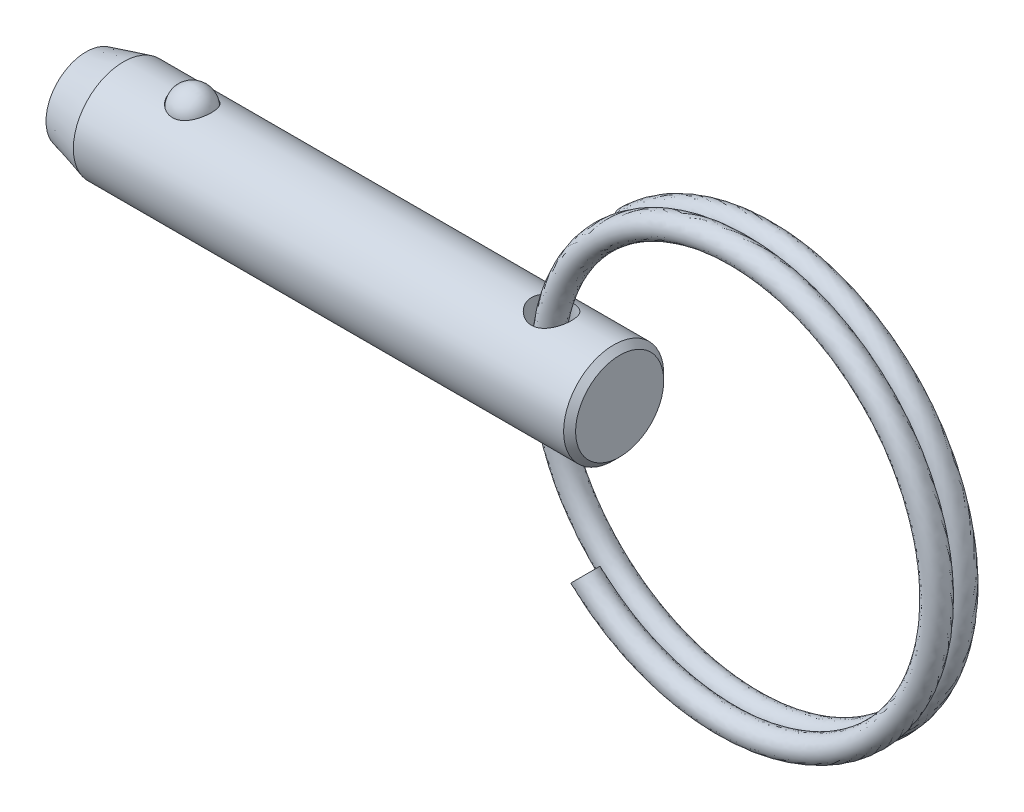
SolidWorks part; units mm, degrees
material "AISI 304"
ref_plane "Front" through (0, 0, 0) normal (0, 0, 1) x (1, 0, 0)
ref_plane "Top" through (0, 0, 0) normal (0, 1, 0) x (1, 0, 0)
ref_plane "Right" through (0, 0, 0) normal (1, 0, 0) x (0, 0, -1)
sketch "Sketch1" plane through (0, 0, 0) normal (0, 0, 1) x (1, 0, 0)
  line L0 (5.588, 2.794) -> (5.207, 3.175)
  line L1 (5.207, 3.175) -> (5.588, 3.175) construction
  line L4 (5.588, 2.794) -> (5.588, 0)
  line L5 (5.588, 3.175) -> (5.588, 2.794) construction
  line L16 (5.207, 3.175) -> (-25.8749, 3.175)
  line L17 (-28.2448, 3.175) -> (-28.2448, 2.54) construction
  line L19 (-25.8749, 3.175) -> (-28.2448, 3.175) construction
  line L22 (-28.2448, -3.175) -> (-25.8749, -3.175) construction
  line L23 (-21.5103, 2.8575) -> (-21.5103, -2.8575) construction
  line L24 (-28.2448, 0) -> (5.588, 0)
  line L27 (5.588, 0) -> (8.382, 0) construction
  line L29 (-28.2448, 0) -> (-28.2448, -2.54) construction
  line L36 (0, 0) -> (0, 3.175) construction
  line L37 (-28.2448, 2.54) -> (-28.2448, 0)
  line L38 (-25.8749, -3.175) -> (5.588, -3.175) construction
  line L39 (-28.2448, -2.54) -> (-28.2448, -3.175) construction
  line L40 (-25.8749, 3.175) -> (-28.2448, 2.54)
  line L42 (-25.8749, -3.175) -> (-28.2448, -2.54) construction
  line L43 (-25.8749, 3.175) -> (-25.8749, -3.175) construction
  circle A2 centre (-21.5103, 2.8575) radius 1.2319 construction
  point P35 (-20.32, 3.175)
  dimension "D2" = 5.715
  dimension "D11" = 0.9144
  dimension "A" = 6.35
  dimension "D" = 5.588
  dimension "E" = 7.2644
  dimension "D3" = 0.381
  dimension "Useable Length" = 20.32
  dimension "D12" = 5.08
  dimension "C" = 7.9248
  dimension "A1" = 15
revolve "Revolve1" add sketch "Sketch1" angle 360 about L27
sketch "Sketch2" plane through (0, 0, 0) normal (0, 0, 1) x (1, 0, 0)
  line L0 (-20.253, 2.8575) -> (-22.7676, 2.8575)
  line L1 (-21.5103, 4.0894) -> (-21.5103, 4.1148) construction
  line L2 (-20.253, 2.8575) -> (-17.7384, 2.8575) construction
  circle A0 centre (-21.5103, 2.8575) radius 1.2319 construction
  circle A1 centre (-21.5103, 2.8575) radius 1.2319 construction
  arc A2 (-22.7676, 2.8575) -> (-20.253, 2.8575) centre (-21.5103, 2.8575) cw
  dimension "D1" = 0.0254
revolve "Cut-Revolve1" cut sketch "Sketch2" angle 360 about L2
sketch "Sketch3" plane through (0, 0, 0) normal (0, 0, 1) x (1, 0, 0)
  line L0 (-20.2784, 2.8575) -> (-22.7422, 2.8575)
  line L1 (-20.2784, 2.8575) -> (-17.8146, 2.8575) construction
  circle A0 centre (-21.5103, 2.8575) radius 1.2319 construction
  arc A1 (-20.2784, 2.8575) -> (-22.7422, 2.8575) centre (-21.5103, 2.8575) ccw
revolve "Revolve2" add sketch "Sketch3" angle 360 about L1
sketch "Sketch4" plane through (0, 0, 0) normal (0, 0, 1) x (1, 0, 0)
  line L1 (1.27, -3.175) -> (2.54, -3.175)
  line L2 (1.27, -3.175) -> (1.27, 3.175)
  line L3 (1.27, 3.175) -> (2.54, 3.175)
  line L4 (2.54, -3.175) -> (2.54, 3.175)
  line L5 (1.27, -3.175) -> (1.27, -4.445) construction
  line L6 (2.54, 3.175) -> (5.588, 3.175) construction
  line L8 (0, -3.175) -> (0, 3.175) construction
  line L9 (0, 0) -> (1.27, 0) construction
  line L11 (1.27, 0) -> (2.54, 0) construction
  line L12 (5.207, 3.175) -> (-25.8749, 3.175) construction
  line L14 (-25.8749, -3.175) -> (5.588, -3.175) construction
  dimension "D1" = 2.54
revolve "Cut-Revolve2" cut sketch "Sketch4" angle 360 about L2
sketch "Sketch5" plane through (0, 0, 0) normal (0, 0, 1) x (1, 0, 0)
  line L0 (0, 0) -> (0.293, 0) construction
  line L1 (0.293, 0) -> (0.293, 3.175) construction
  line L2 (5.207, 3.175) -> (-25.8749, 3.175) construction
  line L3 (13.755, 0) -> (27.217, 0) construction
  line L4 (2.54, 3.175) -> (2.247, 3.175) construction
  line L5 (1.27, 3.175) -> (2.54, 3.175) construction
  line L6 (0.6728, 3.175) -> (0.6728, -3.175) construction
  line L7 (0.293, 3.175) -> (0, 3.175) construction
  line L8 (1.27, -3.175) -> (2.54, -3.175) construction
  line L9 (0.6728, -3.175) -> (2.54, -3.175) construction
  line L10 (0.293, 0) -> (13.755, 0) construction
  line L11 (13.755, 0) -> (8.7098, -10.8195) construction
  line L12 (2.247, 3.175) -> (0.6728, 3.175) construction
  line L13 (13.755, 11.938) -> (13.755, 13.462) construction
  line L14 (8.7098, -10.8195) -> (8.3878, -11.5101) construction
  circle A0 centre (13.755, 0) radius 13.462
  circle A1 centre (13.755, 0) radius 11.938 construction
  circle A2 centre (13.755, 0) radius 12.7 construction
  point P26 (13.755, 12.7)
  dimension "D1" = 65
  dimension "R Ring Dia" = 25.4
  dimension "Ring OD" = 1.524
curve "Helix/Spiral1" pitch 1.5494 height 1.3557 radius 13.462 left hand yes centre (13.755, 0, 0) axis (0, 0, -1) start towards (1, 0, 0)
sketch "Sketch6" plane through (114.0038, 0, 0) normal (0, 1, 0) x (0, 0, -1)
  line L0 (0, 112.1868) -> (0, 112.9488) construction
  line L1 (0, 112.9488) -> (0, 113.7108) construction
  circle A0 centre (0, 112.9488) radius 0.762
  dimension "D1" = 1.524
sketch "Sketch7" plane through (0, 0, 0) normal (0, 0, 1) x (1, 0, 0)
  circle A0 centre (13.755, 0) radius 13.462 construction
  circle A1 centre (13.755, 0) radius 13.462
curve "Helix/Spiral2" pitch 1.5494 height 1.3557 radius 13.462 left hand yes centre (13.755, 0, 0) axis (0, 0, 1) start towards (1, 0, 0)
sweep "Sweep1" add profiles "Sketch6" path "Helix/Spiral1"
sweep "Sweep2" add profiles "Sketch6<2>" path "Helix/Spiral2"
sketch "Sketch6<2>" plane through (114.0038, 0, 0) normal (0, 1, 0) x (0, 0, -1) same geometry as "Sketch6"
ref_plane "Plane1" through (0, -10.8195, 0) normal (0, 1, 0) x (-1, 0, 0)
sketch "Sketch8" plane through (0, -10.8195, 0) normal (0, 1, 0) x (-1, 0, 0)
  line L0 (143.6902, 0) -> (-8.7098, 0) construction
  line L1 (10.3402, -0.7779) -> (4.5066, -0.7779)
  line L2 (3.5004, -0.9415) -> (-7.2005, -4.517)
  line L3 (-7.2005, 4.517) -> (3.5004, 0.9415)
  line L4 (4.5066, 0.7779) -> (130.4738, 0.7779)
  line L5 (131.48, 0.9415) -> (142.1809, 4.517)
  line L6 (124.6402, -0.7779) -> (130.4738, -0.7779)
  line L7 (131.48, -0.9415) -> (142.1809, -4.517)
  line L8 (10.3402, -0.7779) -> (10.3402, 0.7779) construction
  arc A0 (-7.2005, 4.517) -> (-7.2005, -4.517) centre (-8.7098, 0) ccw
  arc A1 (142.1809, -4.517) -> (142.1809, 4.517) centre (143.6902, 0) ccw
  arc A2 (4.5066, -0.7779) -> (3.5004, -0.9415) centre (4.5066, -3.9529) ccw
  arc A3 (3.5004, 0.9415) -> (4.5066, 0.7779) centre (4.5066, 3.9529) ccw
  arc A4 (130.4738, -0.7779) -> (131.48, -0.9415) centre (130.4738, -3.9529) cw
  arc A5 (130.4738, 0.7779) -> (131.48, 0.9415) centre (130.4738, 3.9529) ccw
  point P6 (10.3402, 0)
  point P16 (3.9902, -0.7779)
  point P20 (3.9902, 0.7779)
  point P23 (130.9902, -0.7779)
  point P26 (130.9902, 0.7779)
  dimension "D2" = 4.7625
  dimension "D3" = 1.5557
  dimension "D6" = 3.175
  dimension "Lanyard Length" = 152.4
  dimension "D4" = 6.35
  dimension "D5" = 12.7
ref_plane "Plane2" through (-10.3402, 0, 0) normal (1, 0, 0) x (0, 0, -1)
sketch "Sketch9" plane through (-10.3402, 0, 0) normal (1, 0, 0) x (0, 0, -1)
  circle A0 centre (0.7779, -10.8195) radius 0.7779
sweep "Sweep3" [suppressed] add profiles "Sketch9" path "Sketch8"
sketch "Sketch10" [suppressed] plane through (-10.3402, 0, 0) normal (1, 0, 0) x (0, 0, -1)
  arc A0 (-0.3849, -10.1482) -> (-0.3849, -11.4908) centre (-0.7779, -10.8195) ccw
  circle A1 centre (0.7779, -10.8195) radius 0.7779
  arc A2 (0.3849, -11.4908) -> (0.3849, -10.1482) centre (0.7779, -10.8195) ccw
  arc A3 (-0.3849, -11.4908) -> (0.3849, -11.4908) centre (0, -12.1485) cw
  arc A4 (-0.3869, -9.3301) -> (-0.3869, -12.3089) centre (-0.7779, -10.8195) ccw
  arc A5 (0.3869, -12.3089) -> (0.3869, -9.3301) centre (0.7779, -10.8195) ccw
  circle A6 centre (-0.7779, -10.8195) radius 1.5399 construction
  circle A7 centre (-0.7779, -10.8195) radius 0.7779 construction
  arc A8 (-0.3849, -10.1482) -> (0.3849, -10.1482) centre (0, -9.4905) ccw
  arc A9 (-0.3869, -9.3301) -> (0.3869, -9.3301) centre (0, -7.856) ccw
  arc A10 (0.3869, -12.3089) -> (-0.3869, -12.3089) centre (0, -13.783) ccw
  point P4 (-0.034, -10.2746)
  point P8 (2.3178, -10.502)
  point P9 (0.762, -10.502)
  dimension "D3" = 1.524
  dimension "D4" = 0.762
  dimension "D2" = 0.762
  dimension "D1" = 0
extrude "Extrude1" [suppressed] add sketch "Sketch10" along normal blind 5.715 separate body
sketch "Sketch11" [suppressed] plane through (-124.6402, 0, 0) normal (1, 0, 0) x (0, 0, -1)
  arc A4 (-0.3849, -10.1482) -> (-0.3849, -11.4908) centre (-0.7779, -10.8195) ccw
  arc A5 (0.3849, -11.4908) -> (-0.3849, -11.4908) centre (0, -12.1485) ccw
  arc A6 (0.3849, -11.4908) -> (0.3849, -10.1482) centre (0.7779, -10.8195) ccw
  arc A7 (-0.3849, -10.1482) -> (0.3849, -10.1482) centre (0, -9.4905) ccw
  arc A8 (-0.3849, -10.1482) -> (-0.3849, -11.4908) centre (-0.7779, -10.8195) ccw
  arc A9 (0.3849, -11.4908) -> (-0.3849, -11.4908) centre (0, -12.1485) ccw
  arc A10 (0.3849, -11.4908) -> (0.3849, -10.1482) centre (0.7779, -10.8195) ccw
  arc A11 (-0.3849, -10.1482) -> (0.3849, -10.1482) centre (0, -9.4905) ccw
  arc A12 (-0.3869, -9.3301) -> (-0.3869, -12.3089) centre (-0.7779, -10.8195) ccw
  arc A13 (0.3869, -12.3089) -> (-0.3869, -12.3089) centre (0, -13.783) ccw
  arc A14 (0.3869, -12.3089) -> (0.3869, -9.3301) centre (0.7779, -10.8195) ccw
  arc A15 (-0.3869, -9.3301) -> (0.3869, -9.3301) centre (0, -7.856) ccw
  arc A16 (-0.3869, -9.3301) -> (-0.3869, -12.3089) centre (-0.7779, -10.8195) ccw
  arc A17 (0.3869, -12.3089) -> (-0.3869, -12.3089) centre (0, -13.783) ccw
  arc A18 (0.3869, -12.3089) -> (0.3869, -9.3301) centre (0.7779, -10.8195) ccw
  arc A19 (-0.3869, -9.3301) -> (0.3869, -9.3301) centre (0, -7.856) ccw
  dimension "D1" = 0
  dimension "D2" = 0
extrude "Extrude2" [suppressed] add sketch "Sketch11" against normal blind 5.715 separate body
sketch "Sketch12" plane through (0, -10.8195, 0) normal (0, 1, 0) x (-1, 0, 0)
  line L0 (174.4712, -5.2864) -> (168.9086, -5.2864) construction
  line L1 (174.4712, -5.9214) -> (158.1026, -5.9214)
  line L2 (174.4712, -5.9214) -> (174.4712, -4.6514)
  line L3 (174.4712, -4.6514) -> (158.3265, -4.6514)
  line L4 (158.1026, -5.9214) -> (158.3265, -4.6514) construction
  line L5 (158.1026, -5.9214) -> (142.7212, -0.3231)
  line L6 (168.9086, -5.2864) -> (158.2146, -5.2864) construction
  line L7 (158.3265, -4.6514) -> (143.1555, 0.8704)
  line L8 (142.7212, -0.3231) -> (143.1555, 0.8704)
  line L9 (158.2146, -5.2864) -> (148.1655, -1.6289) construction
  line L10 (148.1655, -1.6289) -> (142.9383, 0.2737) construction
  arc A0 (142.1809, -4.517) -> (142.1809, 4.517) centre (143.6902, 0) ccw construction
  dimension "D1" = 20
  dimension "D2" = 31.75
  dimension "D3" = 1.27
  dimension "D4" = 5.5626
extrude "Extrude3" [suppressed] add sketch "Sketch12" along normal mid plane 12.7 separate body
sketch "Sketch13" [suppressed] plane through (0, 0, -4.6514) normal (0, 0, 1) x (1, 0, 0)
  line L0 (-174.4712, -10.8195) -> (-158.3265, -10.8195) construction
  line L1 (-172.4782, -4.4695) -> (-174.4712, -4.4695)
  line L2 (-174.4712, -4.4695) -> (-158.3265, -4.4695) construction
  line L3 (-174.4712, -4.4695) -> (-176.4642, -4.4695)
  line L4 (-176.4642, -4.4695) -> (-176.4642, -17.1695)
  line L5 (-176.4642, -17.1695) -> (-174.4712, -17.1695)
  line L6 (-174.4712, -17.1695) -> (-172.4782, -17.1695)
  line L7 (-174.4712, -17.1695) -> (-158.3265, -17.1695) construction
  arc A0 (-172.4782, -4.4695) -> (-172.4782, -17.1695) centre (-163.3587, -10.8195) ccw
  circle A1 centre (-168.9086, -10.8195) radius 2.5781
  dimension "D1" = 5.1562
  dimension "D2" = 11.1125
extrude "Extrude4" [suppressed] cut sketch "Sketch13" against normal up to surface (1.27 mm away)
sketch "Sketch14" [suppressed] plane through (-17.0257, 0, 46.7778) normal (-0.342, 0, 0.9397) x (0.9397, 0, 0.342)
  line L3 (-136.2175, -4.4695) -> (-134.2245, -4.4695)
  line L4 (-134.2245, -4.4695) -> (-132.2315, -4.4695)
  line L5 (-132.2315, -4.4695) -> (-132.2315, -17.1695)
  line L6 (-132.2315, -17.1695) -> (-134.2245, -17.1695)
  line L7 (-134.2245, -17.1695) -> (-136.2175, -17.1695)
  line L8 (-134.2245, -4.4695) -> (-134.2245, -17.1695) construction
  line L9 (-150.3692, -4.4695) -> (-134.2245, -4.4695) construction
  line L10 (-150.4811, -10.8195) -> (-139.7871, -10.8195) construction
  arc A0 (-136.2175, -17.1695) -> (-136.2175, -4.4695) centre (-145.337, -10.8195) ccw
  circle A1 centre (-139.7871, -10.8195) radius 2.5781
  dimension "D1" = 5.1562
  dimension "D2" = 11.1125
extrude "Extrude6" [suppressed] cut sketch "Sketch14" against normal up to surface (1.27 mm away)
sketch "Sketch15" [suppressed] plane through (0, 0, 0) normal (0, 0, 1) x (1, 0, 0)
  line L1 (-258.031, -4.4695) -> (-99.281, -4.4695)
  line L2 (-258.031, -4.4695) -> (-270.731, -17.1695)
  line L3 (-270.731, -17.1695) -> (-111.981, -17.1695)
  line L4 (-99.281, -4.4695) -> (-111.981, -17.1695)
  line L5 (-325.1006, -4.4695) -> (-310.949, -4.4695) construction
  line L6 (-325.1006, -17.1695) -> (-310.949, -17.1695) construction
  circle A0 centre (-321.531, -10.8195) radius 2.5781 construction
  dimension "D1" = 63.5
  dimension "D2" = 158.75
  dimension "D3" = 45
extrude "Extrude7" [suppressed] cut sketch "Sketch15" against normal through all and the other way through all
move or copy body "Body-Move/Copy1" [suppressed] bodies to move or copy 147 151 144 copy no translate (152.4, 0, 0)
sketch "Sketch16" [suppressed] plane through (0, 0, 0) normal (0, 0, 1) x (1, 0, 0)
  line L0 (-111.981, -6.057) -> (-111.981, -9.232) construction
  line L1 (-111.981, -9.232) -> (-109.441, -8.2795) construction
  line L2 (-109.441, -8.2795) -> (-114.521, -13.3595) construction
  line L3 (-114.521, -13.3595) -> (-111.981, -12.407) construction
  line L4 (-111.981, -12.407) -> (-111.981, -15.582) construction
  line L5 (-112.7589, -11.5974) -> (-111.2032, -10.0416) construction
  line L6 (-105.631, -15.582) -> (-105.631, -12.407) construction
  line L7 (-105.631, -12.407) -> (-108.171, -13.3595) construction
  line L8 (-108.171, -13.3595) -> (-103.091, -8.2795) construction
  line L9 (-103.091, -8.2795) -> (-105.631, -9.232) construction
  line L10 (-105.631, -9.232) -> (-105.631, -6.057) construction
  line L11 (-104.8532, -10.0416) -> (-106.4089, -11.5974) construction
  line L14 (-4.7291, -10.8195) -> (-283.0963, -10.8195) construction
  dimension "D1" = 3.175
  dimension "D2" = 3.175
  dimension "D3" = 5.08
  dimension "D4" = 1.5875
equation "\"D12@Sketch1\"=\"A@Sketch1\" * 0.80"
equation "\"D2@Sketch1\"=\"A@Sketch1\" * 0.9"
equation "\"D1@Sketch4\" = \"A@Sketch1\" / 2.5"
equation "\"Ring OD@Sketch5\" = \"R Ring Dia@Sketch5\" * 0.06"
equation "\"D4@Helix/Spiral1\"=\"Ring OD@Sketch5\" + 0.001"
equation "\"D1@Sketch6\"=\"Ring OD@Sketch5\""
equation "\"D4@Helix/Spiral2\" = \"D4@Helix/Spiral1\""
equation "\"D5@Helix/Spiral2\" = \"D5@Helix/Spiral1\""
equation "\"D1@Sketch14\" = \"D1@Sketch13\""
equation "\"D2@Sketch14\" = \"D2@Sketch13\""
